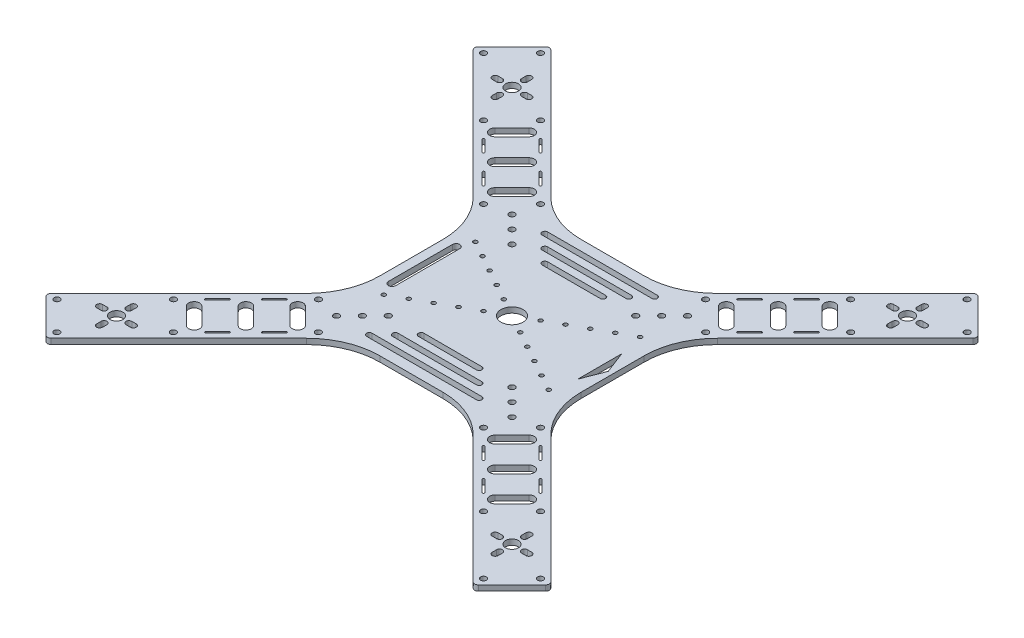
SolidWorks part; units mm, degrees
ref_plane "前视基准面" through (0, 0, 0) normal (0, 0, 1) x (1, 0, 0)
ref_plane "上视基准面" through (0, 0, 0) normal (0, 1, 0) x (1, 0, 0)
ref_plane "右视基准面" through (0, 0, 0) normal (1, 0, 0) x (0, 0, -1)
other "Configuration Table"
sketch "草图1" plane through (0, 0, 0) normal (0, 1, 0) x (1, 0, 0)
  line L0 (-17.2183, 55) -> (17.2183, 55)
  line L1 (-55, 17.2183) -> (-55, -17.2183)
  line L2 (55, 17.2183) -> (55, -17.2183)
  line L3 (-17.2183, -55) -> (17.2183, -55)
  line L4 (0, 55) -> (0, -55) construction
  line L5 (55, 55) -> (-55, -55) construction
  line L6 (45.5025, 66.7157) -> (116.6726, 137.8858)
  line L7 (-137.8858, -116.6726) -> (-116.6726, -137.8858)
  line L8 (116.6726, 137.8858) -> (137.8858, 116.6726)
  line L9 (66.7157, 45.5025) -> (137.8858, 116.6726)
  line L10 (55, 55) -> (108.033, 108.033) construction
  line L11 (55, 55) -> (58.5355, 58.5355)
  line L12 (-116.6726, 137.8858) -> (-45.5025, 66.7157)
  line L13 (-116.6726, 137.8858) -> (-137.8858, 116.6726)
  line L14 (-137.8858, 116.6726) -> (-66.7157, 45.5025)
  line L15 (137.8858, -116.6726) -> (116.6726, -137.8858)
  line L16 (66.7157, -45.5025) -> (137.8858, -116.6726)
  line L17 (116.6726, -137.8858) -> (45.5025, -66.7157)
  line L18 (-137.8858, -116.6726) -> (-66.7157, -45.5025)
  line L19 (-116.6726, -137.8858) -> (-45.5025, -66.7157)
  line L20 (68.0815, 77.2739) -> (77.2739, 68.0815) construction
  line L21 (53.9393, 63.1317) -> (63.1317, 53.9393) construction
  line L22 (70.2028, 79.3952) -> (79.3952, 70.2028)
  line L23 (56.0607, 65.253) -> (65.253, 56.0607)
  line L24 (51.818, 61.0104) -> (61.0104, 51.818)
  line L25 (65.9602, 75.1525) -> (75.1525, 65.9602)
  line L26 (82.2236, 91.416) -> (91.416, 82.2236) construction
  line L27 (84.3449, 93.5373) -> (93.5373, 84.3449)
  line L28 (80.1023, 89.2947) -> (89.2947, 80.1023)
  line L29 (45.1005, 60.6569) -> (84.6985, 100.2548) construction
  line L30 (45.1005, 60.6569) -> (60.6569, 45.1005) construction
  line L31 (84.6985, 100.2548) -> (100.2548, 84.6985) construction
  line L32 (60.6569, 45.1005) -> (100.2548, 84.6985) construction
  line L33 (45.1005, 60.6569) -> (100.2548, 84.6985) construction
  line L34 (84.6985, 100.2548) -> (60.6569, 45.1005) construction
  line L35 (68.0815, 77.2739) -> (77.2739, 68.0815)
  line L36 (108.033, 117.233) -> (108.033, 114.833) construction
  line L37 (117.233, 108.033) -> (114.833, 108.033) construction
  line L38 (109.633, 117.233) -> (109.633, 114.833)
  line L39 (106.433, 117.233) -> (106.433, 114.833)
  line L40 (117.233, 106.433) -> (114.833, 106.433)
  line L41 (117.233, 109.633) -> (114.833, 109.633)
  line L42 (108.033, 98.833) -> (108.033, 101.233) construction
  line L43 (106.433, 98.833) -> (106.433, 101.233)
  line L44 (109.633, 98.833) -> (109.633, 101.233)
  line L45 (98.833, 108.033) -> (101.233, 108.033) construction
  line L46 (98.833, 109.633) -> (101.233, 109.633)
  line L47 (98.833, 106.433) -> (101.233, 106.433)
  line L48 (55, -55) -> (58.5355, -58.5355)
  line L49 (77.2739, -68.0815) -> (68.0815, -77.2739)
  line L50 (55, -55) -> (108.033, -108.033) construction
  line L51 (60.6569, -45.1005) -> (100.2548, -84.6985) construction
  line L52 (60.6569, -45.1005) -> (45.1005, -60.6569) construction
  line L53 (100.2548, -84.6985) -> (84.6985, -100.2548) construction
  line L54 (45.1005, -60.6569) -> (84.6985, -100.2548) construction
  line L55 (60.6569, -45.1005) -> (84.6985, -100.2548) construction
  line L56 (100.2548, -84.6985) -> (45.1005, -60.6569) construction
  line L57 (63.1317, -53.9393) -> (53.9393, -63.1317) construction
  line L58 (65.253, -56.0607) -> (56.0607, -65.253)
  line L59 (61.0104, -51.818) -> (51.818, -61.0104)
  line L60 (77.2739, -68.0815) -> (68.0815, -77.2739) construction
  line L61 (79.3952, -70.2028) -> (70.2028, -79.3952)
  line L62 (75.1525, -65.9602) -> (65.9602, -75.1525)
  line L63 (91.416, -82.2236) -> (82.2236, -91.416) construction
  line L64 (93.5373, -84.3449) -> (84.3449, -93.5373)
  line L65 (89.2947, -80.1023) -> (80.1023, -89.2947)
  line L66 (117.233, -108.033) -> (114.833, -108.033) construction
  line L67 (117.233, -109.633) -> (114.833, -109.633)
  line L68 (117.233, -106.433) -> (114.833, -106.433)
  line L69 (108.033, -117.233) -> (108.033, -114.833) construction
  line L70 (106.433, -117.233) -> (106.433, -114.833)
  line L71 (109.633, -117.233) -> (109.633, -114.833)
  line L72 (98.833, -108.033) -> (101.233, -108.033) construction
  line L73 (98.833, -106.433) -> (101.233, -106.433)
  line L74 (98.833, -109.633) -> (101.233, -109.633)
  line L75 (108.033, -98.833) -> (108.033, -101.233) construction
  line L76 (109.633, -98.833) -> (109.633, -101.233)
  line L77 (106.433, -98.833) -> (106.433, -101.233)
  line L78 (-55, -55) -> (-58.5355, -58.5355)
  line L79 (-68.0815, -77.2739) -> (-77.2739, -68.0815)
  line L80 (-55, -55) -> (-108.033, -108.033) construction
  line L81 (-45.1005, -60.6569) -> (-84.6985, -100.2548) construction
  line L82 (-45.1005, -60.6569) -> (-60.6569, -45.1005) construction
  line L83 (-84.6985, -100.2548) -> (-100.2548, -84.6985) construction
  line L84 (-60.6569, -45.1005) -> (-100.2548, -84.6985) construction
  line L85 (-45.1005, -60.6569) -> (-100.2548, -84.6985) construction
  line L86 (-84.6985, -100.2548) -> (-60.6569, -45.1005) construction
  line L87 (-53.9393, -63.1317) -> (-63.1317, -53.9393) construction
  line L88 (-56.0607, -65.253) -> (-65.253, -56.0607)
  line L89 (-51.818, -61.0104) -> (-61.0104, -51.818)
  line L90 (-68.0815, -77.2739) -> (-77.2739, -68.0815) construction
  line L91 (-70.2028, -79.3952) -> (-79.3952, -70.2028)
  line L92 (-65.9602, -75.1525) -> (-75.1525, -65.9602)
  line L93 (-82.2236, -91.416) -> (-91.416, -82.2236) construction
  line L94 (-84.3449, -93.5373) -> (-93.5373, -84.3449)
  line L95 (-80.1023, -89.2947) -> (-89.2947, -80.1023)
  line L96 (-108.033, -117.233) -> (-108.033, -114.833) construction
  line L97 (-109.633, -117.233) -> (-109.633, -114.833)
  line L98 (-106.433, -117.233) -> (-106.433, -114.833)
  line L99 (-117.233, -108.033) -> (-114.833, -108.033) construction
  line L100 (-117.233, -106.433) -> (-114.833, -106.433)
  line L101 (-117.233, -109.633) -> (-114.833, -109.633)
  line L102 (-108.033, -98.833) -> (-108.033, -101.233) construction
  line L103 (-106.433, -98.833) -> (-106.433, -101.233)
  line L104 (-109.633, -98.833) -> (-109.633, -101.233)
  line L105 (-98.833, -108.033) -> (-101.233, -108.033) construction
  line L106 (-98.833, -109.633) -> (-101.233, -109.633)
  line L107 (-98.833, -106.433) -> (-101.233, -106.433)
  line L108 (-55, 55) -> (-58.5355, 58.5355)
  line L109 (-77.2739, 68.0815) -> (-68.0815, 77.2739)
  line L110 (-55, 55) -> (-108.033, 108.033) construction
  line L111 (-60.6569, 45.1005) -> (-100.2548, 84.6985) construction
  line L112 (-60.6569, 45.1005) -> (-45.1005, 60.6569) construction
  line L113 (-100.2548, 84.6985) -> (-84.6985, 100.2548) construction
  line L114 (-45.1005, 60.6569) -> (-84.6985, 100.2548) construction
  line L115 (-60.6569, 45.1005) -> (-84.6985, 100.2548) construction
  line L116 (-100.2548, 84.6985) -> (-45.1005, 60.6569) construction
  line L117 (-63.1317, 53.9393) -> (-53.9393, 63.1317) construction
  line L118 (-65.253, 56.0607) -> (-56.0607, 65.253)
  line L119 (-61.0104, 51.818) -> (-51.818, 61.0104)
  line L120 (-77.2739, 68.0815) -> (-68.0815, 77.2739) construction
  line L121 (-79.3952, 70.2028) -> (-70.2028, 79.3952)
  line L122 (-75.1525, 65.9602) -> (-65.9602, 75.1525)
  line L123 (-91.416, 82.2236) -> (-82.2236, 91.416) construction
  line L124 (-93.5373, 84.3449) -> (-84.3449, 93.5373)
  line L125 (-89.2947, 80.1023) -> (-80.1023, 89.2947)
  line L126 (-117.233, 108.033) -> (-114.833, 108.033) construction
  line L127 (-117.233, 109.633) -> (-114.833, 109.633)
  line L128 (-117.233, 106.433) -> (-114.833, 106.433)
  line L129 (-108.033, 117.233) -> (-108.033, 114.833) construction
  line L130 (-106.433, 117.233) -> (-106.433, 114.833)
  line L131 (-109.633, 117.233) -> (-109.633, 114.833)
  line L132 (-98.833, 108.033) -> (-101.233, 108.033) construction
  line L133 (-98.833, 106.433) -> (-101.233, 106.433)
  line L134 (-98.833, 109.633) -> (-101.233, 109.633)
  line L135 (-108.033, 98.833) -> (-108.033, 101.233) construction
  line L136 (-109.633, 98.833) -> (-109.633, 101.233)
  line L137 (-106.433, 98.833) -> (-106.433, 101.233)
  line L142 (-30.0417, 0) -> (30.0417, 0) construction
  line L143 (67.8674, 20.3425) -> (-84.4418, -25.3105) construction
  line L144 (-45, 25) -> (45, 25) construction
  line L145 (-45, 25) -> (-45, -25) construction
  line L146 (45, 25) -> (45, -25) construction
  line L147 (-45, -25) -> (45, -25) construction
  line L148 (-45, 25) -> (45, -25) construction
  line L149 (45, 25) -> (-45, -25) construction
  line L150 (55, 55) -> (47.9289, 47.9289)
  line L151 (-47.9289, 47.9289) -> (47.9289, 47.9289)
  line L152 (-40.8579, 40.8579) -> (40.8579, 40.8579)
  line L153 (-33.7868, 33.7868) -> (33.7868, 33.7868)
  line L154 (-30, 47.9289) -> (30, 47.9289) construction
  line L155 (30, 47.9289) -> (47.9289, 47.9289) construction
  line L156 (-30, 49.4289) -> (30, 49.4289)
  line L157 (-30, 46.4289) -> (30, 46.4289)
  line L158 (30, 47.9289) -> (15.8579, 33.7868) construction
  line L159 (47.9289, 47.9289) -> (33.7868, 33.7868) construction
  line L160 (15.8579, 33.7868) -> (33.7868, 33.7868) construction
  line L161 (-22.9289, 40.8579) -> (22.9289, 40.8579) construction
  line L162 (-22.9289, 42.3579) -> (22.9289, 42.3579)
  line L163 (-22.9289, 39.3579) -> (22.9289, 39.3579)
  line L164 (-15.8579, 33.7868) -> (15.8579, 33.7868) construction
  line L165 (-15.8579, 35.2868) -> (15.8579, 35.2868)
  line L166 (-15.8579, 32.2868) -> (15.8579, 32.2868)
  line L167 (-30, -47.9289) -> (30, -47.9289) construction
  line L168 (-30, -49.4289) -> (30, -49.4289)
  line L169 (-30, -46.4289) -> (30, -46.4289)
  line L170 (-22.9289, -40.8579) -> (22.9289, -40.8579) construction
  line L171 (-22.9289, -42.3579) -> (22.9289, -42.3579)
  line L172 (-22.9289, -39.3579) -> (22.9289, -39.3579)
  line L173 (-15.8579, -33.7868) -> (15.8579, -33.7868) construction
  line L174 (-15.8579, -35.2868) -> (15.8579, -35.2868)
  line L175 (-15.8579, -32.2868) -> (15.8579, -32.2868)
  line L176 (30.0417, 0) -> (52.5417, 0) construction
  line L177 (47.9289, 12) -> (47.9289, -12)
  line L178 (47.9289, -12) -> (52.5417, 0)
  line L179 (47.9289, 12) -> (52.5417, 0)
  line L180 (-30.0417, 0) -> (-48.0417, 0)
  line L181 (-48.0417, 17.5) -> (-48.0417, -17.5) construction
  line L182 (69.4957, 53.9393) -> (75.8597, 60.3033) construction
  line L183 (-46.0417, 17.5) -> (-46.0417, -17.5)
  line L184 (-50.0417, 17.5) -> (-50.0417, -17.5)
  line L185 (85.052, 69.4957) -> (91.416, 75.8597) construction
  line L186 (69.1421, 54.2929) -> (75.5061, 60.6569)
  line L187 (69.8492, 53.5858) -> (76.2132, 59.9497)
  line L188 (84.6985, 69.8492) -> (91.0624, 76.2132)
  line L189 (85.4056, 69.1421) -> (91.7696, 75.5061)
  line L190 (53.9393, 69.4957) -> (60.3033, 75.8597) construction
  line L191 (54.2929, 69.1421) -> (60.6569, 75.5061)
  line L192 (53.5858, 69.8492) -> (59.9497, 76.2132)
  line L193 (69.4957, 85.052) -> (75.8597, 91.416) construction
  line L194 (69.8492, 84.6985) -> (76.2132, 91.0624)
  line L195 (69.1421, 85.4056) -> (75.5061, 91.7696)
  line L196 (53.9393, -69.4957) -> (60.3033, -75.8597) construction
  line L197 (54.2929, -69.1421) -> (60.6569, -75.5061)
  line L198 (53.5858, -69.8492) -> (59.9497, -76.2132)
  line L199 (69.4957, -85.052) -> (75.8597, -91.416) construction
  line L200 (69.8492, -84.6985) -> (76.2132, -91.0624)
  line L201 (69.1421, -85.4056) -> (75.5061, -91.7696)
  line L202 (69.4957, -53.9393) -> (75.8597, -60.3033) construction
  line L203 (69.1421, -54.2929) -> (75.5061, -60.6569)
  line L204 (69.8492, -53.5858) -> (76.2132, -59.9497)
  line L205 (85.052, -69.4957) -> (91.416, -75.8597) construction
  line L206 (84.6985, -69.8492) -> (91.0624, -76.2132)
  line L207 (85.4056, -69.1421) -> (91.7696, -75.5061)
  line L208 (-69.4957, -53.9393) -> (-75.8597, -60.3033) construction
  line L209 (-69.1421, -54.2929) -> (-75.5061, -60.6569)
  line L210 (-69.8492, -53.5858) -> (-76.2132, -59.9497)
  line L211 (-85.052, -69.4957) -> (-91.416, -75.8597) construction
  line L212 (-84.6985, -69.8492) -> (-91.0624, -76.2132)
  line L213 (-85.4056, -69.1421) -> (-91.7696, -75.5061)
  line L214 (-53.9393, -69.4957) -> (-60.3033, -75.8597) construction
  line L215 (-54.2929, -69.1421) -> (-60.6569, -75.5061)
  line L216 (-53.5858, -69.8492) -> (-59.9497, -76.2132)
  line L217 (-69.4957, -85.052) -> (-75.8597, -91.416) construction
  line L218 (-69.8492, -84.6985) -> (-76.2132, -91.0624)
  line L219 (-69.1421, -85.4056) -> (-75.5061, -91.7696)
  line L220 (-53.9393, 69.4957) -> (-60.3033, 75.8597) construction
  line L221 (-54.2929, 69.1421) -> (-60.6569, 75.5061)
  line L222 (-53.5858, 69.8492) -> (-59.9497, 76.2132)
  line L223 (-69.4957, 85.052) -> (-75.8597, 91.416) construction
  line L224 (-69.8492, 84.6985) -> (-76.2132, 91.0624)
  line L225 (-69.1421, 85.4056) -> (-75.5061, 91.7696)
  line L226 (-69.4957, 53.9393) -> (-75.8597, 60.3033) construction
  line L227 (-69.1421, 54.2929) -> (-75.5061, 60.6569)
  line L228 (-69.8492, 53.5858) -> (-76.2132, 59.9497)
  line L229 (-85.052, 69.4957) -> (-91.416, 75.8597) construction
  line L230 (-84.6985, 69.8492) -> (-91.0624, 76.2132)
  line L231 (-85.4056, 69.1421) -> (-91.7696, 75.5061)
  arc A0 (-55, 17.2183) -> (-66.7157, 45.5025) centre (-95, 17.2183) ccw
  arc A1 (55, 17.2183) -> (66.7157, 45.5025) centre (95, 17.2183) cw
  arc A2 (45.5025, 66.7157) -> (17.2183, 55) centre (17.2183, 95) cw
  arc A3 (-17.2183, 55) -> (-45.5025, 66.7157) centre (-17.2183, 95) cw
  arc A4 (66.7157, -45.5025) -> (55, -17.2183) centre (95, -17.2183) cw
  arc A5 (17.2183, -55) -> (45.5025, -66.7157) centre (17.2183, -95) cw
  arc A6 (-17.2183, -55) -> (-45.5025, -66.7157) centre (-17.2183, -95) ccw
  arc A7 (-66.7157, -45.5025) -> (-55, -17.2183) centre (-95, -17.2183) ccw
  circle A8 centre (108.033, 108.033) radius 14 construction
  circle A9 centre (108.033, 108.033) radius 8 construction
  circle A12 centre (116.033, 108.033) radius 1.6 construction
  circle A13 centre (108.033, 100.033) radius 1.6 construction
  circle A14 centre (100.033, 108.033) radius 1.6 construction
  circle A15 centre (108.033, 116.033) radius 1.6 construction
  arc A16 (56.0607, 65.253) -> (51.818, 61.0104) centre (53.9393, 63.1317) ccw
  arc A17 (61.0104, 51.818) -> (65.253, 56.0607) centre (63.1317, 53.9393) ccw
  arc A18 (70.2028, 79.3952) -> (65.9602, 75.1525) centre (68.0815, 77.2739) ccw
  arc A19 (75.1525, 65.9602) -> (79.3952, 70.2028) centre (77.2739, 68.0815) ccw
  arc A20 (84.3449, 93.5373) -> (80.1023, 89.2947) centre (82.2236, 91.416) ccw
  arc A21 (89.2947, 80.1023) -> (93.5373, 84.3449) centre (91.416, 82.2236) ccw
  circle A22 centre (84.6985, 100.2548) radius 1.6
  circle A23 centre (100.2548, 84.6985) radius 1.6
  circle A24 centre (60.6569, 45.1005) radius 1.6
  circle A25 centre (45.1005, 60.6569) radius 1.6
  circle A26 centre (108.033, 108.033) radius 3.5
  arc A27 (109.633, 117.233) -> (106.433, 117.233) centre (108.033, 117.233) ccw
  arc A28 (106.433, 114.833) -> (109.633, 114.833) centre (108.033, 114.833) ccw
  arc A29 (117.233, 106.433) -> (117.233, 109.633) centre (117.233, 108.033) ccw
  arc A30 (114.833, 109.633) -> (114.833, 106.433) centre (114.833, 108.033) ccw
  arc A31 (106.433, 98.833) -> (109.633, 98.833) centre (108.033, 98.833) ccw
  arc A32 (109.633, 101.233) -> (106.433, 101.233) centre (108.033, 101.233) ccw
  arc A33 (98.833, 109.633) -> (98.833, 106.433) centre (98.833, 108.033) ccw
  arc A34 (101.233, 106.433) -> (101.233, 109.633) centre (101.233, 108.033) ccw
  circle A35 centre (116.5183, 132.0746) radius 1.6
  circle A36 centre (132.0746, 116.5183) radius 1.6
  circle A37 centre (100.2548, -84.6985) radius 1.6
  circle A38 centre (84.6985, -100.2548) radius 1.6
  circle A39 centre (45.1005, -60.6569) radius 1.6
  circle A40 centre (60.6569, -45.1005) radius 1.6
  circle A41 centre (108.033, -108.033) radius 3.5
  circle A42 centre (132.0746, -116.5183) radius 1.6
  circle A43 centre (116.5183, -132.0746) radius 1.6
  circle A44 centre (108.033, -108.033) radius 14 construction
  circle A45 centre (108.033, -108.033) radius 8 construction
  circle A46 centre (108.033, -116.033) radius 1.6 construction
  circle A47 centre (100.033, -108.033) radius 1.6 construction
  circle A48 centre (108.033, -100.033) radius 1.6 construction
  circle A49 centre (116.033, -108.033) radius 1.6 construction
  arc A50 (65.253, -56.0607) -> (61.0104, -51.818) centre (63.1317, -53.9393) ccw
  arc A51 (51.818, -61.0104) -> (56.0607, -65.253) centre (53.9393, -63.1317) ccw
  arc A52 (79.3952, -70.2028) -> (75.1525, -65.9602) centre (77.2739, -68.0815) ccw
  arc A53 (65.9602, -75.1525) -> (70.2028, -79.3952) centre (68.0815, -77.2739) ccw
  arc A54 (93.5373, -84.3449) -> (89.2947, -80.1023) centre (91.416, -82.2236) ccw
  arc A55 (80.1023, -89.2947) -> (84.3449, -93.5373) centre (82.2236, -91.416) ccw
  arc A56 (117.233, -109.633) -> (117.233, -106.433) centre (117.233, -108.033) ccw
  arc A57 (114.833, -106.433) -> (114.833, -109.633) centre (114.833, -108.033) ccw
  arc A58 (106.433, -117.233) -> (109.633, -117.233) centre (108.033, -117.233) ccw
  arc A59 (109.633, -114.833) -> (106.433, -114.833) centre (108.033, -114.833) ccw
  arc A60 (98.833, -106.433) -> (98.833, -109.633) centre (98.833, -108.033) ccw
  arc A61 (101.233, -109.633) -> (101.233, -106.433) centre (101.233, -108.033) ccw
  arc A62 (109.633, -98.833) -> (106.433, -98.833) centre (108.033, -98.833) ccw
  arc A63 (106.433, -101.233) -> (109.633, -101.233) centre (108.033, -101.233) ccw
  circle A64 centre (-84.6985, -100.2548) radius 1.6
  circle A65 centre (-100.2548, -84.6985) radius 1.6
  circle A66 centre (-60.6569, -45.1005) radius 1.6
  circle A67 centre (-45.1005, -60.6569) radius 1.6
  circle A68 centre (-108.033, -108.033) radius 3.5
  circle A69 centre (-116.5183, -132.0746) radius 1.6
  circle A70 centre (-132.0746, -116.5183) radius 1.6
  circle A71 centre (-108.033, -108.033) radius 14 construction
  circle A72 centre (-108.033, -108.033) radius 8 construction
  circle A73 centre (-116.033, -108.033) radius 1.6 construction
  circle A74 centre (-108.033, -100.033) radius 1.6 construction
  circle A75 centre (-100.033, -108.033) radius 1.6 construction
  circle A76 centre (-108.033, -116.033) radius 1.6 construction
  arc A77 (-56.0607, -65.253) -> (-51.818, -61.0104) centre (-53.9393, -63.1317) ccw
  arc A78 (-61.0104, -51.818) -> (-65.253, -56.0607) centre (-63.1317, -53.9393) ccw
  arc A79 (-70.2028, -79.3952) -> (-65.9602, -75.1525) centre (-68.0815, -77.2739) ccw
  arc A80 (-75.1525, -65.9602) -> (-79.3952, -70.2028) centre (-77.2739, -68.0815) ccw
  arc A81 (-84.3449, -93.5373) -> (-80.1023, -89.2947) centre (-82.2236, -91.416) ccw
  arc A82 (-89.2947, -80.1023) -> (-93.5373, -84.3449) centre (-91.416, -82.2236) ccw
  arc A83 (-109.633, -117.233) -> (-106.433, -117.233) centre (-108.033, -117.233) ccw
  arc A84 (-106.433, -114.833) -> (-109.633, -114.833) centre (-108.033, -114.833) ccw
  arc A85 (-117.233, -106.433) -> (-117.233, -109.633) centre (-117.233, -108.033) ccw
  arc A86 (-114.833, -109.633) -> (-114.833, -106.433) centre (-114.833, -108.033) ccw
  arc A87 (-106.433, -98.833) -> (-109.633, -98.833) centre (-108.033, -98.833) ccw
  arc A88 (-109.633, -101.233) -> (-106.433, -101.233) centre (-108.033, -101.233) ccw
  arc A89 (-98.833, -109.633) -> (-98.833, -106.433) centre (-98.833, -108.033) ccw
  arc A90 (-101.233, -106.433) -> (-101.233, -109.633) centre (-101.233, -108.033) ccw
  circle A91 centre (-100.2548, 84.6985) radius 1.6
  circle A92 centre (-84.6985, 100.2548) radius 1.6
  circle A93 centre (-45.1005, 60.6569) radius 1.6
  circle A94 centre (-60.6569, 45.1005) radius 1.6
  circle A95 centre (-108.033, 108.033) radius 3.5
  circle A96 centre (-132.0746, 116.5183) radius 1.6
  circle A97 centre (-116.5183, 132.0746) radius 1.6
  circle A98 centre (-108.033, 108.033) radius 14 construction
  circle A99 centre (-108.033, 108.033) radius 8 construction
  circle A100 centre (-108.033, 116.033) radius 1.6 construction
  circle A101 centre (-100.033, 108.033) radius 1.6 construction
  circle A102 centre (-108.033, 100.033) radius 1.6 construction
  circle A103 centre (-116.033, 108.033) radius 1.6 construction
  arc A104 (-65.253, 56.0607) -> (-61.0104, 51.818) centre (-63.1317, 53.9393) ccw
  arc A105 (-51.818, 61.0104) -> (-56.0607, 65.253) centre (-53.9393, 63.1317) ccw
  arc A106 (-79.3952, 70.2028) -> (-75.1525, 65.9602) centre (-77.2739, 68.0815) ccw
  arc A107 (-65.9602, 75.1525) -> (-70.2028, 79.3952) centre (-68.0815, 77.2739) ccw
  arc A108 (-93.5373, 84.3449) -> (-89.2947, 80.1023) centre (-91.416, 82.2236) ccw
  arc A109 (-80.1023, 89.2947) -> (-84.3449, 93.5373) centre (-82.2236, 91.416) ccw
  arc A110 (-117.233, 109.633) -> (-117.233, 106.433) centre (-117.233, 108.033) ccw
  arc A111 (-114.833, 106.433) -> (-114.833, 109.633) centre (-114.833, 108.033) ccw
  arc A112 (-106.433, 117.233) -> (-109.633, 117.233) centre (-108.033, 117.233) ccw
  arc A113 (-109.633, 114.833) -> (-106.433, 114.833) centre (-108.033, 114.833) ccw
  arc A114 (-98.833, 106.433) -> (-98.833, 109.633) centre (-98.833, 108.033) ccw
  arc A115 (-101.233, 109.633) -> (-101.233, 106.433) centre (-101.233, 108.033) ccw
  arc A116 (-109.633, 98.833) -> (-106.433, 98.833) centre (-108.033, 98.833) ccw
  arc A117 (-106.433, 101.233) -> (-109.633, 101.233) centre (-108.033, 101.233) ccw
  circle A118 centre (47.9289, 47.9289) radius 1.6
  circle A119 centre (40.8579, 40.8579) radius 1.6
  circle A120 centre (33.7868, 33.7868) radius 1.6
  circle A121 centre (47.9289, -47.9289) radius 1.6
  circle A122 centre (40.8579, -40.8579) radius 1.6
  circle A123 centre (33.7868, -33.7868) radius 1.6
  circle A124 centre (-47.9289, -47.9289) radius 1.6
  circle A125 centre (-40.8579, -40.8579) radius 1.6
  circle A126 centre (-33.7868, -33.7868) radius 1.6
  circle A127 centre (-47.9289, 47.9289) radius 1.6
  circle A128 centre (-40.8579, 40.8579) radius 1.6
  circle A129 centre (-33.7868, 33.7868) radius 1.6
  arc A130 (-30, 49.4289) -> (-30, 46.4289) centre (-30, 47.9289) ccw
  arc A131 (30, 46.4289) -> (30, 49.4289) centre (30, 47.9289) ccw
  arc A132 (-22.9289, 42.3579) -> (-22.9289, 39.3579) centre (-22.9289, 40.8579) ccw
  arc A133 (22.9289, 39.3579) -> (22.9289, 42.3579) centre (22.9289, 40.8579) ccw
  arc A134 (-15.8579, 35.2868) -> (-15.8579, 32.2868) centre (-15.8579, 33.7868) ccw
  arc A135 (15.8579, 32.2868) -> (15.8579, 35.2868) centre (15.8579, 33.7868) ccw
  arc A136 (-30, -49.4289) -> (-30, -46.4289) centre (-30, -47.9289) cw
  arc A137 (30, -46.4289) -> (30, -49.4289) centre (30, -47.9289) cw
  arc A138 (-22.9289, -42.3579) -> (-22.9289, -39.3579) centre (-22.9289, -40.8579) cw
  arc A139 (22.9289, -39.3579) -> (22.9289, -42.3579) centre (22.9289, -40.8579) cw
  arc A140 (-15.8579, -35.2868) -> (-15.8579, -32.2868) centre (-15.8579, -33.7868) cw
  arc A141 (15.8579, -32.2868) -> (15.8579, -35.2868) centre (15.8579, -33.7868) cw
  arc A142 (-46.0417, 17.5) -> (-50.0417, 17.5) centre (-48.0417, 17.5) ccw
  arc A143 (-50.0417, -17.5) -> (-46.0417, -17.5) centre (-48.0417, -17.5) ccw
  arc A144 (69.1421, 54.2929) -> (69.8492, 53.5858) centre (69.4957, 53.9393) ccw
  arc A145 (76.2132, 59.9497) -> (75.5061, 60.6569) centre (75.8597, 60.3033) ccw
  arc A146 (84.6985, 69.8492) -> (85.4056, 69.1421) centre (85.052, 69.4957) ccw
  arc A147 (91.7696, 75.5061) -> (91.0624, 76.2132) centre (91.416, 75.8597) ccw
  arc A148 (54.2929, 69.1421) -> (53.5858, 69.8492) centre (53.9393, 69.4957) cw
  arc A149 (59.9497, 76.2132) -> (60.6569, 75.5061) centre (60.3033, 75.8597) cw
  arc A150 (69.8492, 84.6985) -> (69.1421, 85.4056) centre (69.4957, 85.052) cw
  arc A151 (75.5061, 91.7696) -> (76.2132, 91.0624) centre (75.8597, 91.416) cw
  arc A152 (54.2929, -69.1421) -> (53.5858, -69.8492) centre (53.9393, -69.4957) ccw
  arc A153 (59.9497, -76.2132) -> (60.6569, -75.5061) centre (60.3033, -75.8597) ccw
  arc A154 (69.8492, -84.6985) -> (69.1421, -85.4056) centre (69.4957, -85.052) ccw
  arc A155 (75.5061, -91.7696) -> (76.2132, -91.0624) centre (75.8597, -91.416) ccw
  arc A156 (69.1421, -54.2929) -> (69.8492, -53.5858) centre (69.4957, -53.9393) cw
  arc A157 (76.2132, -59.9497) -> (75.5061, -60.6569) centre (75.8597, -60.3033) cw
  arc A158 (84.6985, -69.8492) -> (85.4056, -69.1421) centre (85.052, -69.4957) cw
  arc A159 (91.7696, -75.5061) -> (91.0624, -76.2132) centre (91.416, -75.8597) cw
  arc A160 (-69.1421, -54.2929) -> (-69.8492, -53.5858) centre (-69.4957, -53.9393) ccw
  arc A161 (-76.2132, -59.9497) -> (-75.5061, -60.6569) centre (-75.8597, -60.3033) ccw
  arc A162 (-84.6985, -69.8492) -> (-85.4056, -69.1421) centre (-85.052, -69.4957) ccw
  arc A163 (-91.7696, -75.5061) -> (-91.0624, -76.2132) centre (-91.416, -75.8597) ccw
  arc A164 (-54.2929, -69.1421) -> (-53.5858, -69.8492) centre (-53.9393, -69.4957) cw
  arc A165 (-59.9497, -76.2132) -> (-60.6569, -75.5061) centre (-60.3033, -75.8597) cw
  arc A166 (-69.8492, -84.6985) -> (-69.1421, -85.4056) centre (-69.4957, -85.052) cw
  arc A167 (-75.5061, -91.7696) -> (-76.2132, -91.0624) centre (-75.8597, -91.416) cw
  arc A168 (-54.2929, 69.1421) -> (-53.5858, 69.8492) centre (-53.9393, 69.4957) ccw
  arc A169 (-59.9497, 76.2132) -> (-60.6569, 75.5061) centre (-60.3033, 75.8597) ccw
  arc A170 (-69.8492, 84.6985) -> (-69.1421, 85.4056) centre (-69.4957, 85.052) ccw
  arc A171 (-75.5061, 91.7696) -> (-76.2132, 91.0624) centre (-75.8597, 91.416) ccw
  arc A172 (-69.1421, 54.2929) -> (-69.8492, 53.5858) centre (-69.4957, 53.9393) cw
  arc A173 (-76.2132, 59.9497) -> (-75.5061, 60.6569) centre (-75.8597, 60.3033) cw
  arc A174 (-84.6985, 69.8492) -> (-85.4056, 69.1421) centre (-85.052, 69.4957) cw
  arc A175 (-91.7696, 75.5061) -> (-91.0624, 76.2132) centre (-91.416, 75.8597) cw
  circle A176 centre (-45, 25) radius 1.1
  circle A177 centre (45, 25) radius 1.1
  circle A178 centre (45, -25) radius 1.1
  circle A179 centre (-45, -25) radius 1.1
  circle A180 centre (-36.2584, 20.1436) radius 1.1
  circle A181 centre (-27.5169, 15.2871) radius 1.1
  circle A182 centre (-18.7753, 10.4307) radius 1.1
  circle A183 centre (-10.0337, 5.5743) radius 1.1
  circle A184 centre (36.2584, 20.1436) radius 1.1
  circle A185 centre (27.5169, 15.2871) radius 1.1
  circle A186 centre (18.7753, 10.4307) radius 1.1
  circle A187 centre (10.0337, 5.5743) radius 1.1
  circle A188 centre (-36.2584, -20.1436) radius 1.1
  circle A189 centre (-27.5169, -15.2871) radius 1.1
  circle A190 centre (-18.7753, -10.4307) radius 1.1
  circle A191 centre (-10.0337, -5.5743) radius 1.1
  circle A192 centre (36.2584, -20.1436) radius 1.1
  circle A193 centre (27.5169, -15.2871) radius 1.1
  circle A194 centre (18.7753, -10.4307) radius 1.1
  circle A195 centre (10.0337, -5.5743) radius 1.1
  circle A197 centre (0, 0) radius 6
  point P1 (0, 0)
  point P2 (0, 0)
  point P14 (0, 0)
  point P54 (108.033, 108.033)
  point P56 (72.6777, 72.6777)
  point P58 (58.5355, 58.5355)
  point P64 (72.6777, 72.6777)
  point P71 (86.8198, 86.8198)
  point P89 (0, 0)
  point P90 (108.033, 116.033)
  point P98 (116.033, 108.033)
  point P105 (108.033, 100.033)
  point P112 (100.033, 108.033)
  point P117 (108.033, 108.033)
  point P121 (0, 0)
  point P137 (108.033, -108.033)
  point P139 (72.6777, -72.6777)
  point P141 (58.5355, -58.5355)
  point P147 (72.6777, -72.6777)
  point P154 (86.8198, -86.8198)
  point P171 (116.033, -108.033)
  point P179 (108.033, -116.033)
  point P186 (100.033, -108.033)
  point P193 (108.033, -100.033)
  point P198 (108.033, -108.033)
  point P217 (-108.033, -108.033)
  point P219 (-72.6777, -72.6777)
  point P221 (-58.5355, -58.5355)
  point P227 (-72.6777, -72.6777)
  point P234 (-86.8198, -86.8198)
  point P251 (-108.033, -116.033)
  point P259 (-116.033, -108.033)
  point P266 (-108.033, -100.033)
  point P273 (-100.033, -108.033)
  point P278 (-108.033, -108.033)
  point P297 (-108.033, 108.033)
  point P299 (-72.6777, 72.6777)
  point P301 (-58.5355, 58.5355)
  point P307 (-72.6777, 72.6777)
  point P314 (-86.8198, 86.8198)
  point P331 (-116.033, 108.033)
  point P339 (-108.033, 116.033)
  point P346 (-100.033, 108.033)
  point P353 (-108.033, 100.033)
  point P358 (-108.033, 108.033)
  point P362 (0, 0)
  point P378 (22.9289, 40.8579)
  point P397 (0, 0)
  point P399 (0, 47.9289)
  point P404 (18.2028, 64.3461)
  point P407 (0, 40.8579)
  point P414 (0, 33.7868)
  point P421 (0, -47.9289)
  point P428 (0, -40.8579)
  point P435 (0, -33.7868)
  point P444 (47.9289, 0)
  point P447 (72.6777, 57.1213)
  point P448 (88.234, 72.6777)
  point P449 (-48.0417, 0)
  point P458 (72.6777, 57.1213)
  point P463 (88.234, 72.6777)
  point P470 (57.1213, 72.6777)
  point P477 (72.6777, 88.234)
  point P489 (57.1213, -72.6777)
  point P494 (72.6777, -88.234)
  point P501 (72.6777, -57.1213)
  point P508 (88.234, -72.6777)
  point P517 (-72.6777, -57.1213)
  point P522 (-88.234, -72.6777)
  point P529 (-57.1213, -72.6777)
  point P536 (-72.6777, -88.234)
  point P545 (-57.1213, 72.6777)
  point P550 (-72.6777, 88.234)
  point P557 (-72.6777, 57.1213)
  point P564 (-88.234, 72.6777)
  point P569 (0, 0)
  dimension "D1" = 40
  dimension "D2" = 40
  dimension "D4" = 28
  dimension "D6" = 16
  dimension "D7" = 3.2
  dimension "D8" = 4
  dimension "D10" = 3
  dimension "D13" = 3.2
  dimension "D14" = 7
  dimension "D15" = 4
  dimension "D23" = 3.2
  dimension "D28" = 4
  dimension "D29" = 2.2
  dimension "D30" = 2.2
  dimension "D31" = 2.2
  dimension "D32" = 2.2
  dimension "D37" = 12
  dimension "D3" = 75
  dimension "D9" = 5
  dimension "D11" = 56
  dimension "D12" = 22
  dimension "D18" = 100
  dimension "D19" = 60
  dimension "D20" = 90
  dimension "D21" = 50
  dimension "D22" = 10
  dimension "D26" = 22.5
  dimension "D27" = 18
  dimension "D16" = 2
  dimension "D24" = 3
  dimension "D33" = 5
  dimension "D34" = 5
  dimension "D35" = 5
  dimension "D36" = 5
  dimension "D5" = 2
  dimension "D17" = 4
  dimension "D25" = 4
extrude "凸台-拉伸2" add sketch "草图1" along normal blind 3 contours A7 L18 L7 L19 A6 L3 A5 L17 L15 L16 A4 L2 A1 L9 L8 L6 A2 L0 A3 L12 L13 L14 A0 L1 A171 L225 A170 L224 A169 L222 A168 L221 A163 L213 A162 L212 A161 L210 A160 L209 A155 L201 A154 L200 A153 region at (0, 0, -51.1)
fillet "圆角1" radius 2 1 edges at (137.8858, 1.5, -116.6726)
fillet "圆角2" radius 2 7 edges at (-116.6726, 1.5, -137.8858) (-137.8858, 1.5, -116.6726) (-137.8858, 1.5, 116.6726) (-116.6726, 1.5, 137.8858) (116.6726, 1.5, 137.8858) (137.8858, 1.5, 116.6726) (116.6726, 1.5, -137.8858)
